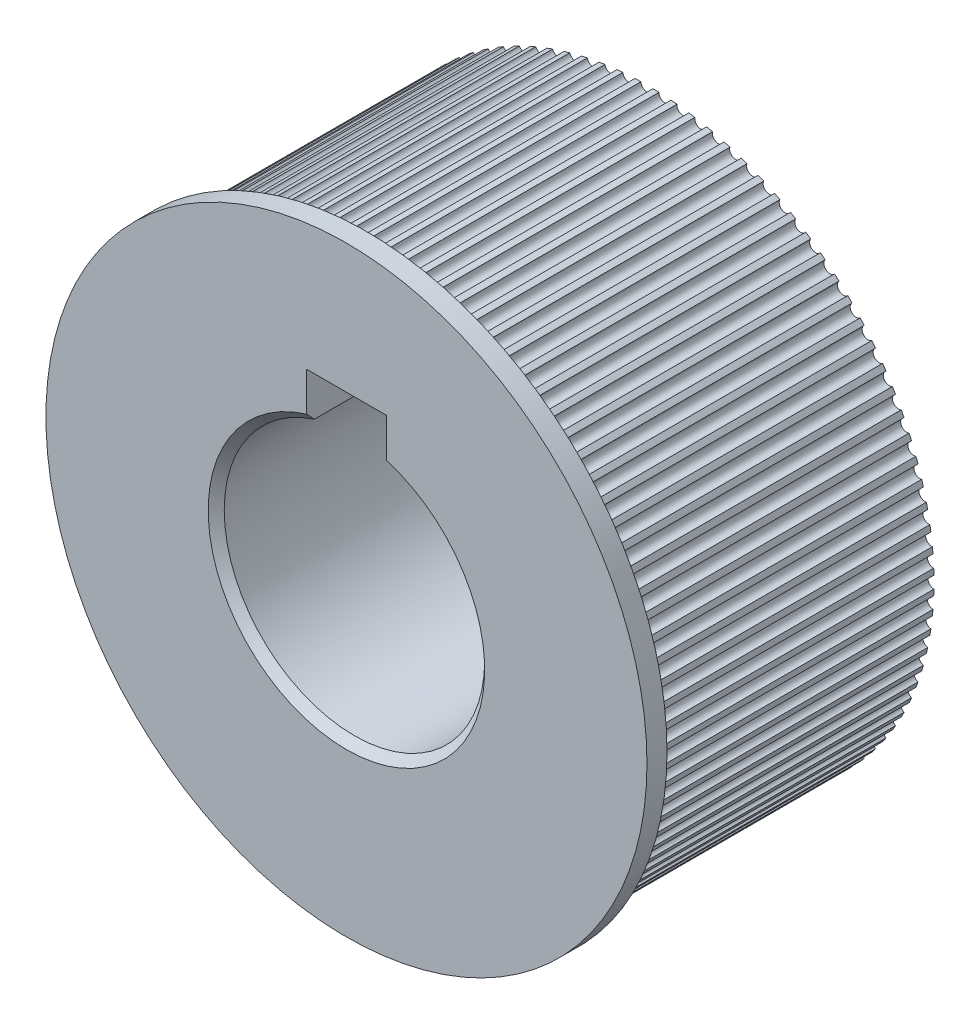
SolidWorks part; units mm, degrees
ref_plane "Přední rovina" through (0, 0, 0) normal (0, 0, 1) x (1, 0, 0)
ref_plane "Horní rovina" through (0, 0, 0) normal (0, 1, 0) x (1, 0, 0)
ref_plane "Pravá rovina" through (0, 0, 0) normal (1, 0, 0) x (0, 0, -1)
sketch "Skica1" plane through (0, 0, 0) normal (0, 0, 1) x (1, 0, 0)
  line L0 (-0.8999, 28.6352) -> (0, 0) construction
  line L1 (0, 0) -> (0.8999, 28.6352) construction
  line L2 (-0.8999, 28.6352) -> (0.8999, 28.6352) construction
  line L3 (-0.8999, 28.6352) -> (-0.4083, 12.9936)
  line L5 (0.4083, 12.9936) -> (0.8999, 28.6352)
  circle A0 centre (0, 0) radius 28.6493 construction
  arc A1 (-0.6, 28.643) -> (0.6, 28.643) centre (0, 28.6493) ccw
  arc A2 (-0.8999, 28.6352) -> (-0.6, 28.643) centre (0, 0) cw
  arc A3 (0.8999, 28.6352) -> (0.6, 28.643) centre (0, 0) ccw
  circle A4 centre (0, 0) radius 13 construction
  arc A5 (-0.4083, 12.9936) -> (0.4083, 12.9936) centre (0, 0) cw
  point P4 (0, 28.6352)
  dimension "D3" = 26
  dimension "D1" = 0.3
  dimension "D2" = 1.2
  dimension "D4" = 3.6
extrude "Přidat vysunutím1" add sketch "Skica1" along normal mid plane 30
pattern_circular "Kruhové pole1" count 100 over 360 about axis through (0, 0, 15) along (0, 0, -1) of "Přidat vysunutím1"
sketch "Skica2" plane through (0, 0, 15) normal (0, 0, 1) x (1, 0, 0)
  line L0 (0, 0) -> (0, 12.3693) construction
  line L1 (-4, 12.3693) -> (4, 12.3693)
  line L2 (-4, 12.3693) -> (-4, 17.1)
  line L3 (-4, 17.1) -> (4, 17.1)
  line L4 (4, 12.3693) -> (4, 17.1)
  circle A1 centre (0, 0) radius 13 construction
  dimension "D2" = 4.1
  dimension "D1" = 8
extrude "Odebrat vysunutím1" cut sketch "Skica2" against normal through all
chamfer "Zkosení1" distance 0.8 angle 45 2 edges at (0, -13, 15) (0, -13, -15)
sketch "Skica3" plane through (0, 0, 15) normal (0, 0, 1) x (1, 0, 0)
  line L0 (4, 13.2076) -> (4, 17.1) construction
  line L1 (4, 17.1) -> (-4, 17.1) construction
  line L2 (-4, 17.1) -> (-4, 13.2076) construction
  line L3 (4, 13.2076) -> (4, 17.1)
  line L4 (4, 17.1) -> (-4, 17.1)
  line L5 (-4, 17.1) -> (-4, 13.2076)
  circle A0 centre (0, 0) radius 30
  arc A1 (-4, 13.2076) -> (4, 13.2076) centre (0, 0) ccw construction
  arc A2 (-4, 13.2076) -> (4, 13.2076) centre (0, 0) ccw
  dimension "D1" = 60
extrude "Přidat vysunutím2" add sketch "Skica3" against normal blind 2
